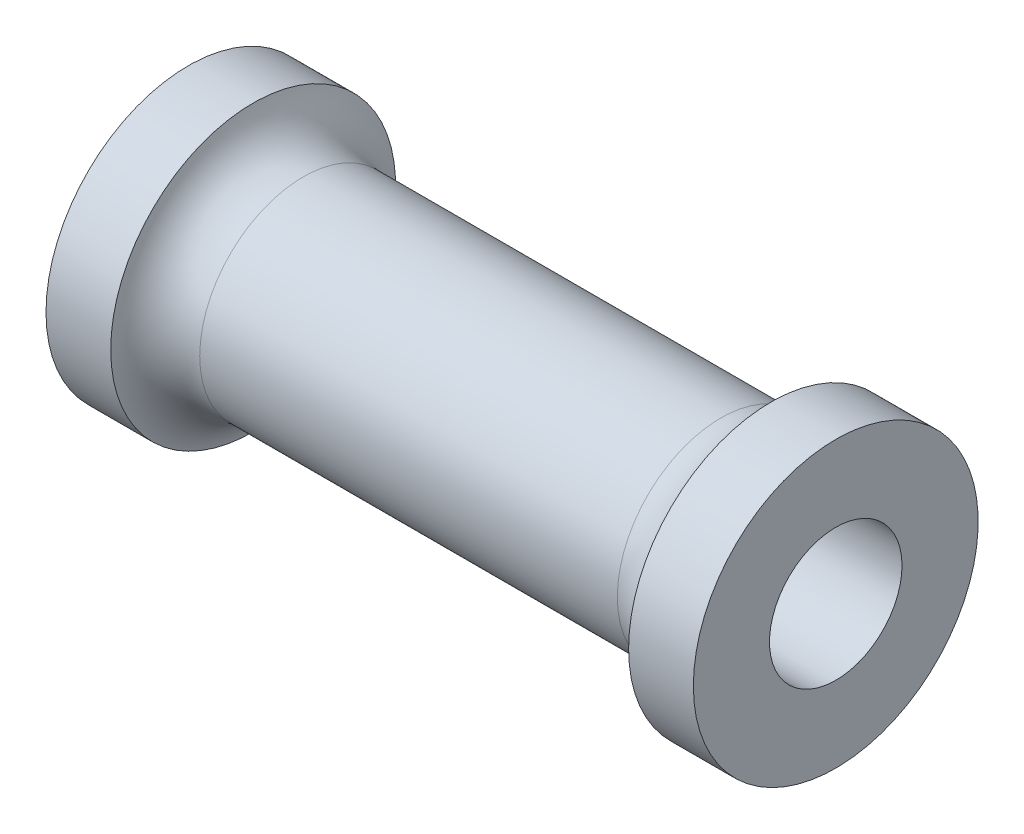
SolidWorks part; units mm, degrees
ref_plane "Front" through (0, 0, 0) normal (0, 0, 1) x (1, 0, 0)
ref_plane "Top" through (0, 0, 0) normal (0, 1, 0) x (1, 0, 0)
ref_plane "Right" through (0, 0, 0) normal (1, 0, 0) x (0, 0, -1)
sketch "Sketch1" plane through (0, 0, 0) normal (0, 0, 1) x (1, 0, 0)
  line L0 (0, 0) -> (63.9778, 0) construction
  line L1 (15.875, 0) -> (15.875, 6.985)
  line L2 (15.875, 6.985) -> (12.7, 6.985)
  line L3 (0, 0) -> (0, 5.08)
  line L4 (0, 0) -> (15.875, 0)
  line L5 (12.7, 5.08) -> (0, 5.08)
  line L6 (12.7, 5.08) -> (12.7, 6.985)
  dimension "D1" = 15.875
  dimension "D2" = 3.175
  dimension "D3" = 6.985
  dimension "D4" = 5.08
revolve "Revolve1" add sketch "Sketch1" angle 360 about L0
mirror "Mirror1" about plane through (0, 0, 0) normal (1, 0, 0) of "Revolve1"
fillet "Fillet1" radius 2.54 2 edges at (12.7, 0, 5.08) (-12.7, 0, 5.08)
sketch "Sketch2" plane through (15.875, 0, 0) normal (1, 0, 0) x (0, 0, -1)
  circle A0 centre (0, 0) radius 3.25
  dimension "D1" = 6.5
extrude "Cut-Extrude1" cut sketch "Sketch2" against normal through all
